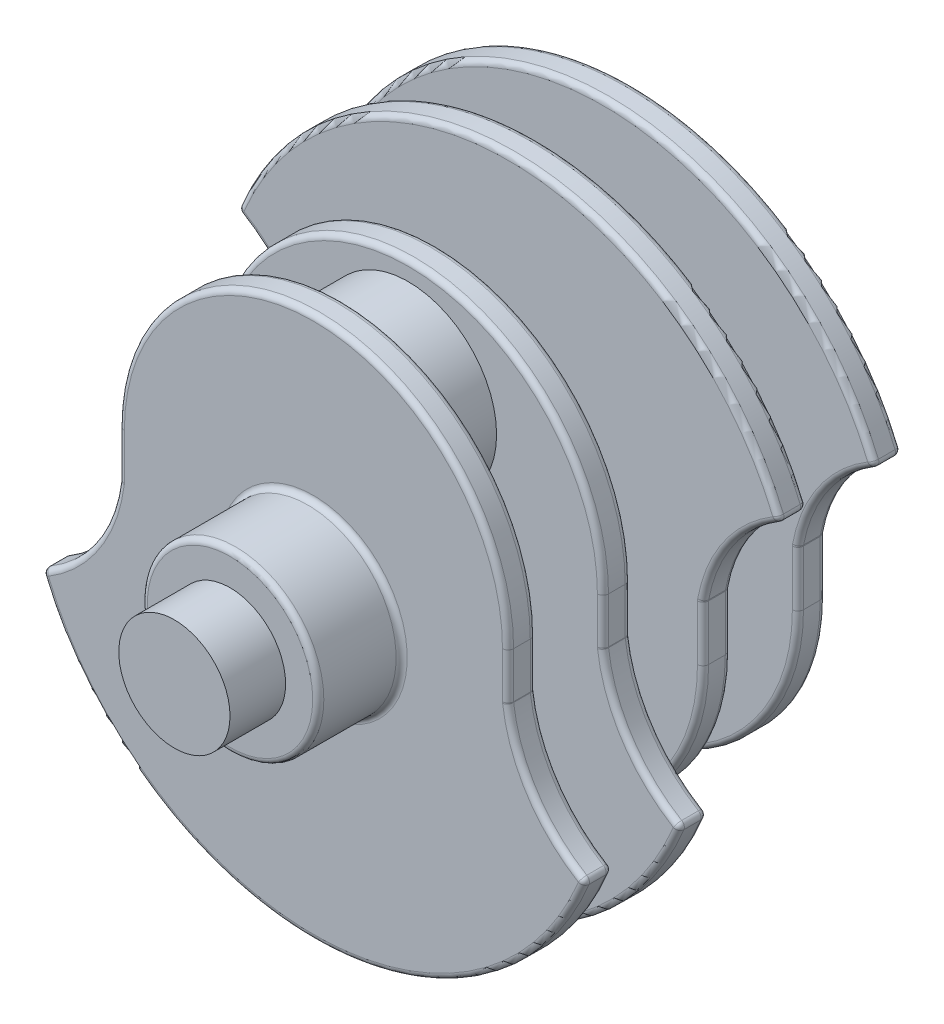
SolidWorks part; units mm, degrees
material "AISI 4340 Steel, normalized"
ref_plane "Front Plane" through (0, 0, 0) normal (0, 0, 1) x (1, 0, 0)
ref_plane "Top Plane" through (0, 0, 0) normal (0, 1, 0) x (1, 0, 0)
ref_plane "Right Plane" through (0, 0, 0) normal (1, 0, 0) x (0, 0, -1)
sketch "Sketch1" plane through (0, 0, 0) normal (0, 0, 1) x (1, 0, 0)
  circle A0 centre (0, 0) radius 31.75
  dimension "D1" = 31.75
extrude "Boss-Extrude1" add sketch "Sketch1" along normal blind 30
sketch "Sketch8" plane through (0, 0, 0) normal (0, 0, -1) x (-1, 0, 0)
  line L0 (-70, 20) -> (-70, 3.36)
  line L1 (70, 20) -> (70, 3.36)
  arc A0 (70, 20) -> (-70, 20) centre (0, 20) ccw
  arc A5 (-97.7839, -38.2532) -> (97.7839, -38.2532) centre (0, 0) ccw
  arc A6 (-70, 3.36) -> (-97.7839, -38.2532) centre (-125, 10) cw
  arc A7 (70, 3.36) -> (97.7839, -38.2532) centre (125, 10) ccw
  dimension "D1" = 70
  dimension "D2" = 105
  dimension "D3" = 20
  dimension "D5" = 10
  dimension "D6" = 125
extrude "Boss-Extrude5" add sketch "Sketch8" along normal blind 10
sketch "Sketch2" plane through (0, 0, 30) normal (0, 0, 1) x (1, 0, 0)
  circle A0 centre (0, 0) radius 20
  dimension "D1" = 20
extrude "Boss-Extrude2" add sketch "Sketch2" along normal blind 20
sketch "Sketch9" plane through (0, 0, -10) normal (0, 0, -1) x (-1, 0, 0)
  circle A0 centre (0, 51.5) radius 31.75
  dimension "D2" = 31.75
  dimension "D1" = 51.5
extrude "Boss-Extrude6" add sketch "Sketch9" along normal blind 24.13
ref_plane "Plane4" through (0, 0, -70.13) normal (0, 0, -1) x (-1, 0, 0)
sketch "Sketch10" plane through (0, 0, -34.13) normal (0, 0, -1) x (-1, 0, 0)
  line L0 (-70, -20) -> (-70, 0)
  line L1 (70, -20) -> (70, 0)
  arc A0 (-70, -20) -> (70, -20) centre (0, -20) ccw
  arc A1 (-70, 0) -> (-97.598, 38.7251) centre (-125, -10) ccw
  arc A2 (70, 0) -> (97.598, 38.7251) centre (125, -10) cw
  arc A3 (-97.598, 38.7251) -> (97.598, 38.7251) centre (0, 0) cw
  dimension "D1" = 70
  dimension "D3" = 105
  dimension "D2" = 20
  dimension "D4" = 125
  dimension "D5" = 10
extrude "Boss-Extrude7" add sketch "Sketch10" along normal blind 10 from surface starting at plane "Plane4"
ref_plane "Plane3" through (0, 0, -104.26) normal (0, 0, -1) x (-1, 0, 0)
sketch "Sketch12" plane through (0, 0, -104.26) normal (0, 0, -1) x (-1, 0, 0)
  line L2 (70, -20) -> (70, 0)
  line L3 (70, -20) -> (70, 0)
  line L4 (-70, 0) -> (-70, -20)
  line L5 (-70, 0) -> (-70, -20)
  arc A12 (-70, -20) -> (70, -20) centre (0, -20) ccw
  arc A13 (97.598, 38.7251) -> (70, 0) centre (125, -10) ccw
  arc A14 (97.598, 38.7251) -> (-97.598, 38.7251) centre (0, 0) ccw
  arc A15 (-70, 0) -> (-97.598, 38.7251) centre (-125, -10) ccw
  arc A16 (-70, -20) -> (70, -20) centre (0, -20) ccw
  arc A17 (97.598, 38.7251) -> (70, 0) centre (125, -10) ccw
  arc A18 (97.598, 38.7251) -> (-97.598, 38.7251) centre (0, 0) ccw
  arc A19 (-70, 0) -> (-97.598, 38.7251) centre (-125, -10) ccw
  dimension "D1" = 0
extrude "Boss-Extrude8" add sketch "Sketch12" along normal blind 10
sketch "Sketch14" plane through (0, 0, -80.13) normal (0, 0, -1) x (-1, 0, 0)
  circle A0 centre (0, -51.5) radius 31.75
  dimension "D2" = 31.75
  dimension "D1" = 51.5
extrude "Boss-Extrude9" add sketch "Sketch14" along normal up to next
sketch "Sketch15" plane through (0, 0, -114.26) normal (0, 0, -1) x (-1, 0, 0)
  circle A1 centre (0, 0) radius 31.75
  circle A2 centre (0, 0) radius 31.75
  dimension "D1" = 0
extrude "Boss-Extrude10" add sketch "Sketch15" along normal blind 30
sketch "Sketch16" plane through (0, 0, -144.26) normal (0, 0, -1) x (-1, 0, 0)
  circle A1 centre (0, 0) radius 20
  circle A2 centre (0, 0) radius 20
  dimension "D1" = 0
extrude "Boss-Extrude11" add sketch "Sketch16" along normal blind 20
sketch "Sketch18" plane through (0, 0, -34.13) normal (0, 0, -1) x (-1, 0, 0)
  line L2 (-70, 20) -> (-70, 3.36)
  line L3 (-70, 20) -> (-70, 3.36)
  line L4 (70, 3.36) -> (70, 20)
  line L5 (70, 3.36) -> (70, 20)
  arc A4 (70, 20) -> (-70, 20) centre (0, 20) ccw
  arc A5 (-97.7839, -38.2532) -> (-70, 3.36) centre (-125, 10) ccw
  arc A6 (-97.7839, -38.2532) -> (97.7839, -38.2532) centre (0, 0) ccw
  arc A7 (70, 3.36) -> (97.7839, -38.2532) centre (125, 10) ccw
  arc A8 (70, 20) -> (-70, 20) centre (0, 20) ccw
  arc A9 (-97.7839, -38.2532) -> (-70, 3.36) centre (-125, 10) ccw
  arc A10 (-97.7839, -38.2532) -> (97.7839, -38.2532) centre (0, 0) ccw
  arc A11 (70, 3.36) -> (97.7839, -38.2532) centre (125, 10) ccw
  dimension "D1" = 0
extrude "Boss-Extrude12" add sketch "Sketch18" along normal blind 10
sketch "Sketch19" plane through (0, 0, -44.13) normal (0, 0, -1) x (-1, 0, 0)
  circle A1 centre (0, 0) radius 31.75
  circle A2 centre (0, 0) radius 31.75
  dimension "D1" = 0
extrude "Boss-Extrude13" add sketch "Sketch19" along normal up to next
fillet "Fillet1" radius 2 32 edges at (0, -105, -34.13) (-78.9263, -20.762, -34.13) (-70, 11.68, -34.13) (70, 11.68, -34.13) (78.9263, -20.762, -34.13) (0, -105, -44.13) (-78.9263, -20.762, -44.13) (-70, 11.68, -44.13) (0, 90, -44.13) (70, 11.68, -44.13) (78.9263, -20.762, -44.13) (97.7839, -38.2532, -39.13) (70, 3.36, -39.13) (-70, 3.36, -39.13) (-97.7839, -38.2532, -39.13) (0, 90, -34.13) (70, 11.68, 0) (78.9263, -20.762, 0) (0, -105, 0) (-78.9263, -20.762, 0) (-70, 11.68, 0) (0, 90, -10) (70, 11.68, -10) (78.9263, -20.762, -10) (0, -105, -10) (-78.9263, -20.762, -10) (-70, 11.68, -10) (-70, 3.36, -5) (-97.7839, -38.2532, -5) (97.7839, -38.2532, -5) (70, 3.36, -5) (0, 90, 0)
fillet "Fillet2" radius 2 16 edges at (0, 105, -104.26) (79.4761, 22.4433, -104.26) (70, -10, -104.26) (0, -90, -104.26) (-70, -10, -104.26) (-79.4761, 22.4433, -104.26) (79.4761, 22.4433, -114.26) (70, -10, -114.26) (0, -90, -114.26) (-70, -10, -114.26) (-79.4761, 22.4433, -114.26) (-97.598, 38.7251, -109.26) (-70, 0, -109.26) (70, 0, -109.26) (97.598, 38.7251, -109.26) (0, 105, -114.26)
fillet "Fillet3" radius 2 16 edges at (70, -10, -70.13) (79.4761, 22.4433, -70.13) (0, 105, -70.13) (-79.4761, 22.4433, -70.13) (-70, -10, -70.13) (0, -90, -70.13) (70, -10, -80.13) (79.4761, 22.4433, -80.13) (-79.4761, 22.4433, -80.13) (-70, -10, -80.13) (0, -90, -80.13) (70, 0, -75.13) (97.598, 38.7251, -75.13) (-97.598, 38.7251, -75.13) (-70, 0, -75.13) (0, 105, -80.13)
fillet "Fillet5" radius 2 2 edges at (31.75, 0, 30) (31.75, 0, 0)
fillet "Fillet6" radius 2 2 edges at (-31.75, 0, -114.26) (-31.75, 0, -144.26)
fillet "Fillet9" radius 2 2 edges at (-31.75, -51.5, -80.13) (-31.75, -51.5, -104.26)
ref_plane "Plane5" through (0, 31.75, 0) normal (0, 1, 0) x (1, 0, 0)
equation "\"Crank Radius\" = 51.5mm"
equation "\"D1@Sketch9\"=\"Crank Radius\""
equation "\"D1@Sketch14\"=\"Crank Radius\""
equation "\"Journal Radius\" = 31.75mm"
equation "\"D1@Sketch1\"=\"Journal Radius\""
equation "\"D2@Sketch9\"=\"Journal Radius\""
equation "\"D2@Sketch14\"=\"Journal Radius\""
equation "\"Lobe Thickness\"= 10mm"
equation "\"D1@Boss-Extrude5\"=\"Lobe Thickness\""
equation "\"D1@Boss-Extrude7\"=\"Lobe Thickness\""
equation "\"D1@Boss-Extrude8\"=\"Lobe Thickness\""
equation "\"D1@Boss-Extrude12\"=\"Lobe Thickness\""
